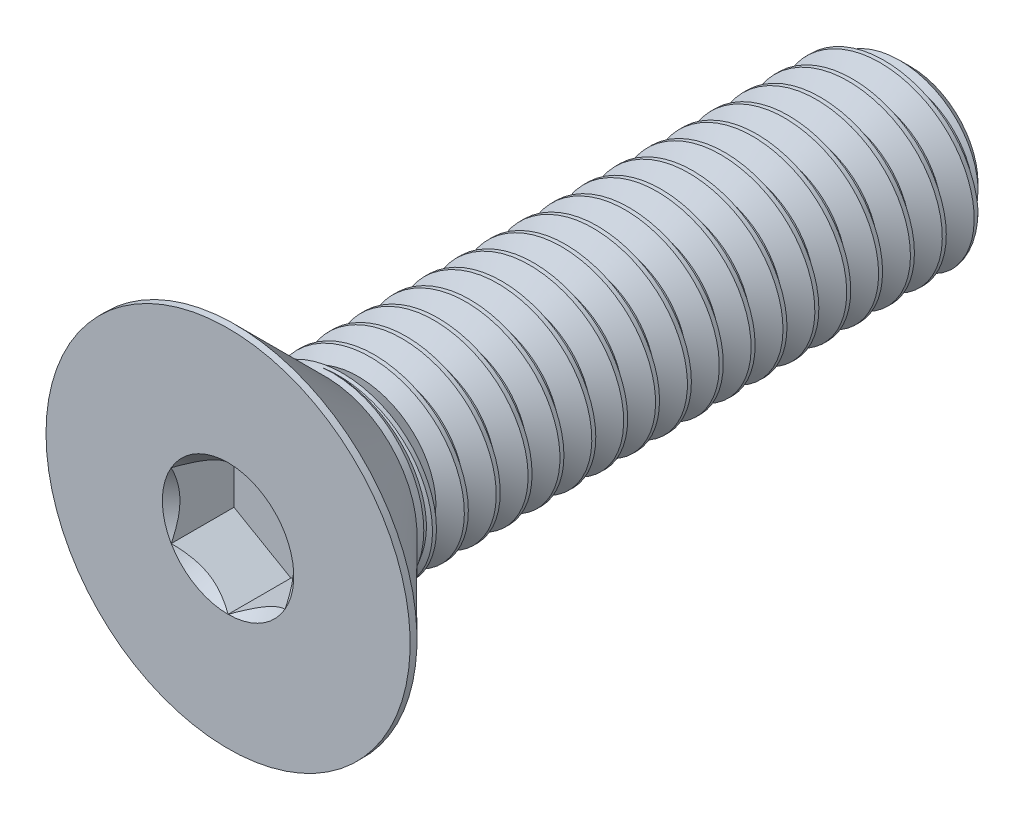
SolidWorks part; units mm, degrees
ref_plane "Front" through (0, 0, 0) normal (0, 0, 1) x (1, 0, 0)
ref_plane "Top" through (0, 0, 0) normal (0, 1, 0) x (1, 0, 0)
ref_plane "Right" through (0, 0, 0) normal (1, 0, 0) x (0, 0, -1)
sketch "Sketch1" plane through (0, 0, 0) normal (0, 0, 1) x (1, 0, 0)
  line L1 (1.25, 0.7217) -> (0, 1.4434)
  line L8 (0, 1.4434) -> (-1.25, 0.7217)
  line L9 (-1.25, 0.7217) -> (-1.25, -0.7217)
  line L10 (-1.25, -0.7217) -> (0, -1.4434)
  line L11 (0, -1.4434) -> (1.25, -0.7217)
  line L12 (1.25, -0.7217) -> (1.25, 0.7217)
  circle A0 centre (0, 0) radius 1.25 construction
  circle A1 centre (0, 0) radius 4
  point P7 (0, 4)
  dimension "Head Diameter" = 8
  dimension "Drive Size" = 2.5
sketch "Sketch2" plane through (0, 0, 0) normal (1, 0, 0) x (0, 0, -1)
  line L6 (-6.35, 0) -> (6.35, 0) construction
  line L8 (6.35, 0) -> (6.35, 2)
  line L9 (6.35, 2) -> (-6.35, 2)
  line L11 (-6.35, 2) -> (-6.35, 0)
  line L13 (-6.35, 2) -> (-6.5, 2)
  line L14 (-6.5, 2) -> (-8.5, 4)
  line L15 (-8.5, 4) -> (-8.65, 4)
  line L16 (-8.65, 4) -> (-8.65, 0)
  line L17 (-8.65, 0) -> (-6.35, 0)
  line L18 (6.35, -2) -> (-6.35, -2)
  line L19 (-8.5, -4) -> (-8.65, -4)
  line L20 (6.3063, 2.0758) -> (6.6563, 1.4696) construction
  line L21 (6.6563, 1.4696) -> (7.0063, 2.0758) construction
  line L22 (7.0063, 2.0758) -> (6.3063, 2.0758) construction
  line L23 (6.3281, 2.0379) -> (6.9844, 2.0379)
  line L24 (6.9844, 2.0379) -> (6.7, 1.5453)
  line L25 (6.7, 1.5453) -> (6.6125, 1.5453)
  line L26 (6.6125, 1.5453) -> (6.3281, 2.0379)
  line L27 (6.6563, 1.5453) -> (6.6563, 1.4696) construction
  line L28 (6.35, 2) -> (6.9625, 2) construction
  line L29 (6.6563, 2.0758) -> (6.6563, 2) construction
  line L30 (5.825, 2) -> (6.35, 1.475)
  point P10 (0, 0)
  point P26 (-7.27, 0)
  point P31 (0.35, -4)
  point P32 (1.35, -4)
  point P33 (-2.65, -4)
  point P38 (4.6, -2)
  point P51 (6.6563, 2.0379)
  point P53 (-8.65, 4)
  dimension "Thread OD" = 4
  dimension "Head Height" = 2.3
  dimension "D1" = 45
  dimension "Length" = 15
  dimension "Hex Depth" = 1.38
  dimension "D2" = 9
  dimension "D3" = 10
  dimension "D4" = 9
  dimension "Thread Pitch" = 0.7
  dimension "D6" = 0.0875
  dimension "D5" = 45
  dimension "D7" = 0.525
  dimension "D8" = 1.75
ref_plane "Plane1" through (0, 0, 6.35) normal (0, 0, 1) x (1, 0, 0)
sketch "Sketch14" plane through (0, 0, 0) normal (1, 0, 0) x (0, 0, -1)
  line L4 (-8.65, 0) -> (-8.65, 4)
  line L5 (-8.65, 4) -> (-8.5, 4)
  line L6 (-8.5, 4) -> (-6.5, 2)
  line L7 (-6.5, 2) -> (-6.35, 2)
  line L8 (-6.35, 2) -> (5.825, 2)
  line L9 (5.825, 2) -> (6.35, 1.475)
  line L10 (6.35, 1.475) -> (6.35, 0)
  line L11 (6.35, 0) -> (-8.65, 0)
revolve "Revolve1" add sketch "Sketch14" angle 360 about L11
sketch "Sketch3" plane through (0, 0, -6.35) normal (0, 0, -1) x (-1, 0, 0)
  circle A0 centre (0, 0) radius 2 construction
  circle A1 centre (0, 0) radius 2
sketch "Sketch5" plane through (0, 0, 8.65) normal (0, 0, 1) x (1, 0, 0)
  line L0 (0, -1.4434) -> (1.25, -0.7217) construction
  line L1 (-1.25, -0.7217) -> (0, -1.4434) construction
  line L2 (-1.25, 0.7217) -> (-1.25, -0.7217) construction
  line L3 (0, 1.4434) -> (-1.25, 0.7217) construction
  line L4 (1.25, 0.7217) -> (0, 1.4434) construction
  line L5 (1.25, -0.7217) -> (1.25, 0.7217) construction
  line L6 (0, -1.4434) -> (1.25, -0.7217)
  line L7 (-1.25, -0.7217) -> (0, -1.4434)
  line L8 (-1.25, 0.7217) -> (-1.25, -0.7217)
  line L9 (0, 1.4434) -> (-1.25, 0.7217)
  line L10 (1.25, 0.7217) -> (0, 1.4434)
  line L11 (1.25, -0.7217) -> (1.25, 0.7217)
extrude "Cut-Extrude2" cut sketch "Sketch5" against normal up to vertex (1.38 mm away) up to point (0, 0, 7.27)
sketch "Sketch6" plane through (0, 0, 8.65) normal (0, 0, 1) x (1, 0, 0)
  circle A0 centre (0, 0) radius 1.4434
extrude "Cut-Extrude3" cut sketch "Sketch6" against normal up to vertex (1.38 mm away) draft 45 up to point (0, 0, 7.27)
split "Split1" trim tools "Plane1" bodies to split 134 resulting bodies 136 137
curve "Helix/Spiral1" pitch 0.7 height 15 radius 2 centre (0, 0, -6.35) axis (0, 0, 1) start towards (0, 1, 0)
sketch "Sketch16" plane through (0, 0, 0) normal (1, 0, 0) x (0, 0, -1)
  line L0 (7.0062, 2.0758) -> (6.3062, 2.0758) construction
  line L1 (6.3062, 2.0758) -> (6.6562, 1.4696) construction
  line L2 (6.6562, 1.4696) -> (7.0062, 2.0758) construction
  line L3 (6.9625, 2) -> (6.35, 2) construction
  line L4 (6.6562, 2.0758) -> (6.6562, 2) construction
  line L5 (6.9844, 2.0379) -> (6.3281, 2.0379) construction
  line L6 (6.7, 1.5453) -> (6.6125, 1.5453) construction
  line L7 (6.6562, 1.5453) -> (6.6562, 1.4696) construction
  line L10 (6.7, 1.5453) -> (6.6125, 1.5453)
  line L15 (6.6125, 1.5453) -> (6.3281, 2.0379)
  line L16 (6.3281, 2.0379) -> (6.9844, 2.0379)
  line L17 (6.9844, 2.0379) -> (6.7, 1.5453)
  point P11 (6.6562, 2.0379)
  dimension "D1" = 0.7
  dimension "D2" = 0.0875
sweep "Cut-Sweep1" cut profiles "Sketch16" path "Helix/Spiral1" align with end faces yes
sketch "Sketch15" plane through (0, 0, 6.35) normal (0, 0, 1) x (1, 0, 0)
  circle A2 centre (0, 0) radius 2
extrude "Boss-Extrude1" add sketch "Sketch15" against normal up to vertex (12.7 mm away) draft 30.9 up to point (0, 0, -6.35)
equation "\"D3@Helix/Spiral1\"=\"Length@Sketch2\""
equation "\"D1\"= \"Head Height@Sketch2\" * .7"
equation "\"D1\"= \"D1\""
equation "\"D4@Helix/Spiral1\" = \"Thread Pitch@Sketch2\""
equation "\"Hex Depth@Sketch2\" = \"Head Height@Sketch2\" * 0.6"
equation "\"D2@Sketch2\" = \"Head Diameter@Sketch1\" * 1.125"
equation "\"D3@Sketch2\" = \"Head Diameter@Sketch1\" * 1.25"
equation "\"D4@Sketch2\" = \"D2@Sketch2\""
equation "\"D6@Sketch2\" = \"Thread Pitch@Sketch2\" / 8"
equation "\"D7@Sketch2\" = \"Thread Pitch@Sketch2\" * 0.75"
equation "\"D8@Sketch2\" = \"Thread Pitch@Sketch2\" * 2.5"
equation "\"D1@Sketch16\"=\"Thread Pitch@Sketch2\""
equation "\"D2@Sketch16\"=\"D1@Sketch16\"/8"
